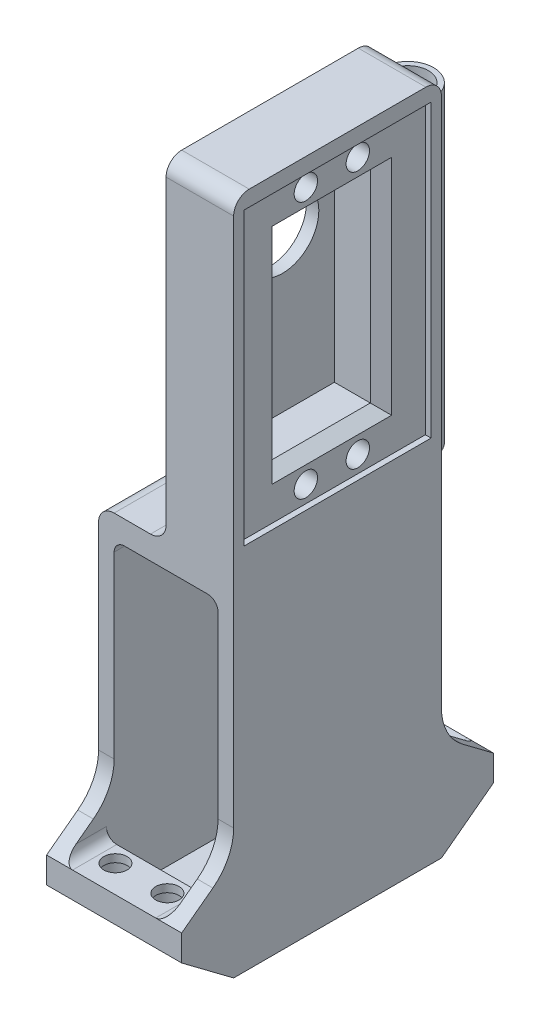
SolidWorks part; units mm, degrees
ref_plane "前视基准面" through (0, 0, 0) normal (0, 0, 1) x (1, 0, 0)
ref_plane "上视基准面" through (0, 0, 0) normal (0, 1, 0) x (1, 0, 0)
ref_plane "右视基准面" through (0, 0, 0) normal (1, 0, 0) x (0, 0, -1)
other "Configuration Table"
sketch "草图1" plane through (0, 0, 0) normal (0, 1, 0) x (1, 0, 0)
  line L0 (0, 0) -> (26, 0)
  line L1 (26, 0) -> (26, -60)
  line L2 (26, -60) -> (0, -60)
  line L3 (0, -60) -> (0, 0)
  dimension "D1" = 26
  dimension "D2" = 60
extrude "凸台-拉伸1" add sketch "草图1" along normal blind 130
sketch "草图3" plane through (0, 0, 0) normal (0, 0, -1) x (-1, 0, 0)
  line L0 (-23, 61.5) -> (-23, 12.5)
  line L1 (-23, 12.5) -> (-3, 12.5)
  line L2 (-3, 12.5) -> (-3, 61.5)
  line L3 (-3, 61.5) -> (-23, 61.5)
  line L4 (-13, 0) -> (-13, 54.0233) construction
  line L5 (-26, 0) -> (0, 0) construction
  point P8 (-13, 12.5)
  dimension "D1" = 20
  dimension "D2" = 49
  dimension "D3" = 12.5
extrude "切除-拉伸1" cut sketch "草图3" against normal blind 180
sketch "草图4" plane through (0, 12.5, 0) normal (0, 1, 0) x (1, 0, 0)
  line L0 (3, -10) -> (23, -10)
  line L1 (23, -10) -> (23, -50)
  line L2 (23, -50) -> (3, -50)
  line L3 (3, -50) -> (3, -10)
  line L4 (13, 12.1227) -> (13, -65.895) construction
  line L5 (-11.7609, -30) -> (44.0627, -30) construction
  line L6 (26, 0) -> (0, 0) construction
  line L7 (0, 0) -> (0, -60) construction
  point P10 (13, 0)
  point P13 (0, -30)
  point P14 (3, -30)
  point P15 (13, -10)
  dimension "D1" = 40
  dimension "D2" = 20
extrude "切除-拉伸3" cut sketch "草图4" against normal offset from surface (10.5 mm away) 2 up to face at (13, 0, 30)
ref_plane "基准面1" through (0, 0, 30) normal (0, 0, -1) x (-1, 0, 0)
sketch "草图14" plane through (0, 0, 0) normal (0, 0, -1) x (-1, 0, 0)
  line L1 (0, 130) -> (0, 0) construction
  line L5 (-26, 130) -> (-26, 0) construction
  line L6 (-23, 12.5) -> (-3, 12.5) construction
  line L7 (0, 12.5) -> (-26, 12.5)
  line L8 (-26, 12.5) -> (-26, 130)
  line L9 (-26, 130) -> (0, 130)
  line L10 (0, 130) -> (0, 12.5)
  line L11 (0, 0) -> (0, 7.5)
  line L12 (0, 7.5) -> (-26, 7.5)
  line L13 (-26, 7.5) -> (-26, 0)
  line L14 (-26, 0) -> (0, 0)
  dimension "D1" = 5
extrude "切除-拉伸13" cut sketch "草图14" against normal blind 10
mirror "镜向1" about plane through (0, 0, 30) normal (0, 0, -1) of "切除-拉伸13"
sketch "草图5" plane through (0, 0, 0) normal (0, -1, 0) x (1, 0, 0)
  line L0 (13, 62.1105) -> (13, -7.3292) construction
  line L1 (0, 60) -> (26, 60) construction
  line L2 (-9.4248, 30) -> (47.5486, 30) construction
  line L3 (0, 10) -> (0, 50) construction
  circle A1 centre (18, 54.75) radius 2.25
  circle A2 centre (8, 54.75) radius 2.25
  circle A3 centre (18, 5.25) radius 2.25
  circle A4 centre (8, 5.25) radius 2.25
  point P6 (13, 60)
  point P11 (0, 30)
  dimension "D1" = 4.5
  dimension "D2" = 10
  dimension "D3" = 49.5
extrude "切除-拉伸4" cut sketch "草图5" against normal up to next
sketch "草图2" plane through (0, 0, 0) normal (0, -1, 0) x (1, 0, 0)
  line L0 (26, 0) -> (0, 0) construction
  line L1 (13, 0) -> (13, 31.858) construction
  circle A0 centre (13, 20) radius 7
  circle A1 centre (18, 5.25) radius 2.25 construction
  dimension "D1" = 14
  dimension "D2" = 14.75
extrude "切除-拉伸2" cut sketch "草图2" against normal up to next
sketch "草图7" plane through (0, 0, 0) normal (-1, 0, 0) x (0, 0, 1)
  line L0 (10, 130) -> (10, 66)
  line L2 (10, 66) -> (50, 66)
  line L4 (50, 66) -> (50, 130)
  line L5 (50, 130) -> (10, 130)
  line L6 (50, 12.5) -> (50, 130) construction
  line L7 (10, 12.5) -> (10, 130) construction
  line L8 (10, 130) -> (50, 130) construction
  dimension "D1" = 64
extrude "切除-拉伸5" cut sketch "草图7" against normal blind 13
sketch "草图6" plane through (26, 0, 0) normal (1, 0, 0) x (0, 0, -1)
  line L0 (-40, 119) -> (-40, 79)
  line L1 (-40, 79) -> (-20, 79)
  line L2 (-20, 79) -> (-20, 119)
  line L3 (-20, 119) -> (-40, 119)
  line L4 (-30, 188.7173) -> (-30, -19.9187) construction
  line L5 (-50, 130) -> (-10, 130) construction
  point P8 (-30, 130)
  point P9 (-30, 119)
  dimension "D1" = 40
  dimension "D2" = 20
  dimension "D3" = 11
extrude "切除-拉伸6" cut sketch "草图6" against normal offset from surface (10.6 mm away) 2.4 up to face at (13, 98, 30)
sketch "草图8" plane through (26, 0, 0) normal (1, 0, 0) x (0, 0, -1)
  line L0 (-48, 127) -> (-48, 71)
  line L1 (-48, 71) -> (-12, 71)
  line L2 (-12, 71) -> (-12, 127)
  line L3 (-12, 127) -> (-48, 127)
  line L4 (-50, 130) -> (-10, 130) construction
  line L5 (-30, 186.2177) -> (-30, 81.6726) construction
  line L6 (-20, 119) -> (-40, 119) construction
  line L7 (-40, 79) -> (-20, 79) construction
  point P8 (-30, 130)
  dimension "D1" = 8
  dimension "D2" = 36
  dimension "D3" = 3
  dimension "D4" = 8
extrude "切除-拉伸7" cut sketch "草图8" against normal offset from surface (1.1 mm away) 9.5 up to face at (15.4, 99, 30)
sketch "草图9" plane through (15.4, 0, 0) normal (1, 0, 0) x (0, 0, -1)
  line L0 (-20, 119) -> (-40, 119) construction
  line L1 (-30, 188.9818) -> (-30, 86.2063) construction
  circle A0 centre (-30, 109.15) radius 7
  point P10 (-30, 119)
  dimension "D1" = 14
  dimension "D2" = 9.85
extrude "切除-拉伸8" cut sketch "草图9" against normal through all
sketch "草图10" plane through (24.9, 0, 0) normal (1, 0, 0) x (0, 0, -1)
  line L0 (-80.8247, 99) -> (29.2748, 99) construction
  line L1 (-40, 119) -> (-40, 79) construction
  line L2 (-30, 184.1499) -> (-30, 80.2039) construction
  line L3 (-12, 127) -> (-48, 127) construction
  circle A0 centre (-25, 123.75) radius 2.25
  circle A1 centre (-35, 123.75) radius 2.25
  circle A2 centre (-35, 74.25) radius 2.25
  circle A3 centre (-25, 74.25) radius 2.25
  point P4 (-40, 99)
  point P9 (-30, 127)
  dimension "D1" = 4.5
  dimension "D2" = 10
  dimension "D3" = 49.5
extrude "切除-拉伸9" cut sketch "草图10" against normal through all
sketch "草图11" plane through (13, 0, 0) normal (-1, 0, 0) x (0, 0, 1)
  circle A0 centre (25, 123.75) radius 3.85
  circle A1 centre (35, 123.75) radius 3.85
  circle A2 centre (35, 74.25) radius 3.85
  circle A3 centre (25, 74.25) radius 3.85
  dimension "D1" = 7.7
  dimension "D2" = 7.7
  dimension "D3" = 7.7
  dimension "D4" = 7.7
extrude "切除-拉伸10" cut sketch "草图11" against normal blind 4.7
sketch "草图12" plane through (0, 7.5, 0) normal (0, -1, 0) x (1, 0, 0)
  circle A0 centre (8, 54.75) radius 3.85
  circle A1 centre (18, 54.75) radius 3.85
  circle A2 centre (18, 5.25) radius 3.85
  circle A3 centre (8, 5.25) radius 3.85
  dimension "D1" = 7.7
  dimension "D2" = 7.7
  dimension "D3" = 7.7
  dimension "D4" = 7.7
extrude "切除-拉伸11" cut sketch "草图12" against normal blind 3.5
sketch "草图16" plane through (26, 0, 0) normal (1, 0, 0) x (0, 0, -1)
  line L0 (0, 7.5) -> (-10, 0)
rib "筋2" sketch "草图16" sketch "草图16" thickness 3 extrusion direction parallel to sketch draft on no parameters "D1"=3
ref_plane "基准面2" through (13, 0, 0) normal (-1, 0, 0) x (0, 0, 1)
mirror "镜向2" about plane through (13, 0, 0) normal (-1, 0, 0) of "筋2"
mirror "镜向3" about plane through (0, 0, 30) normal (0, 0, -1) of "镜向2", "筋2"
ref_plane "基准面3" through (0, 10, 0) normal (0, -1, 0) x (-1, 0, 0)
mirror "镜向4" about plane through (0, 10, 0) normal (0, -1, 0) of "镜向3", "筋2", "镜向2"
sketch "草图17" plane through (0, 130, 0) normal (0, 1, 0) x (1, 0, 0)
  line L0 (13, -10) -> (26, -10) construction
  line L1 (23, -10) -> (3, -10) construction
  line L2 (14.5, -10) -> (15.5, -10)
  line L3 (23.5, -10) -> (24.5, -10)
  arc A0 (15.5, -10) -> (23.5, -10) centre (19.5, -10) cw
  arc A1 (14.5, -10) -> (24.5, -10) centre (19.5, -10) cw
  dimension "D1" = 4
  dimension "D2" = 5
extrude "凸台-拉伸2" add sketch "草图17" against normal blind 60 from offset 4 offset against normal yes
fillet "圆角3" radius 2 6 edges at (23, 12.5, 5) (3, 12.5, 5) (3, 12.5, 55) (23, 12.5, 55) (3, 61.5, 30) (23, 61.5, 30)
chamfer "倒角1" distance 1.5 angle 60 10 edges at (24.9, 119, 30) (24.9, 79, 30) (13, 12.5, 10) (13, 12.5, 50) (24.9, 99, 20) (24.9, 99, 40) (22.4142, 13.0858, 10) (3.5858, 13.0858, 10) (3.5858, 13.0858, 50) (22.4142, 13.0858, 50)
fillet "圆角4" radius 3 8 edges at (23, 1, 50) (3, 1, 50) (23, 1, 10) (3, 1, 10) (19.5, 130, 10) (19.5, 130, 50) (0, 66, 30) (13, 66, 30)
fillet "圆角5" radius 10 4 edges at (24.5, 20, 50) (1.5, 20, 50) (1.5, 20, 10) (24.5, 20, 10)
fillet "圆角6" radius 1 6 edges at (15, 126, 10) (24, 126, 10) (14.5, 96, 10) (24.5, 96, 10) (15, 66, 10) (24, 66, 10)
